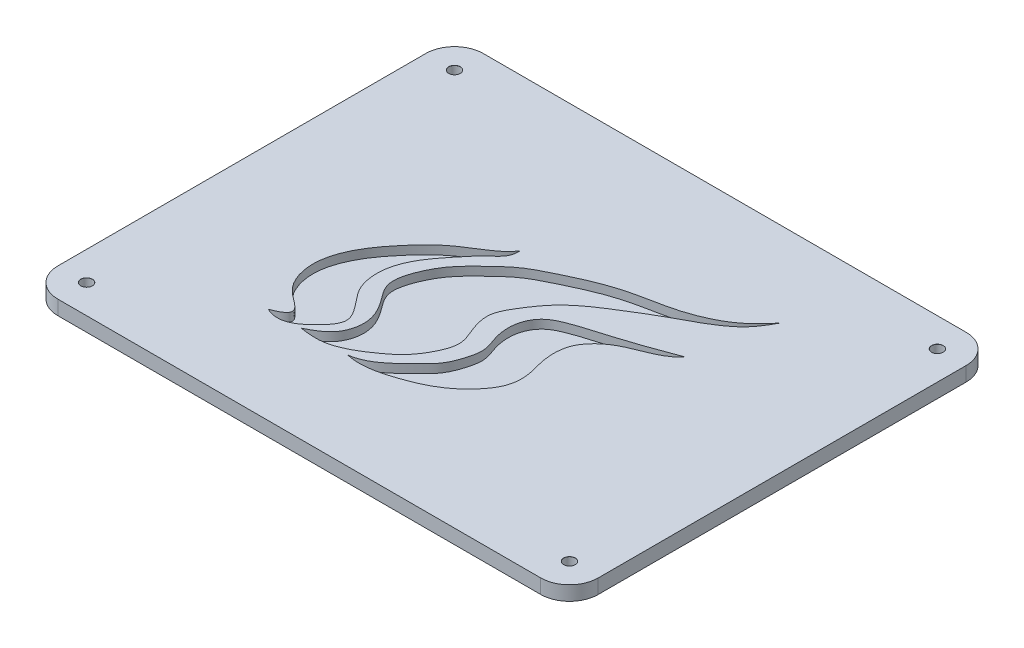
SolidWorks part; units mm, degrees
ref_plane "Plano frontal" through (0, 0, 0) normal (0, 0, 1) x (1, 0, 0)
ref_plane "Plano superior" through (0, 0, 0) normal (0, 1, 0) x (1, 0, 0)
ref_plane "Plano direito" through (0, 0, 0) normal (1, 0, 0) x (0, 0, -1)
ref_plane "Plano1" through (0, -5, 0) normal (0, -1, 0) x (1, 0, 0)
sketch "Esboço1" plane through (0, -5, 0) normal (0, -1, 0) x (1, 0, 0)
  line L0 (0, -148) -> (188, -148)
  line L1 (188, -148) -> (188, 0)
  line L2 (188, 0) -> (0, 0)
  line L3 (0, 0) -> (0, -148)
extrude "Ressalto-extrusão1" add sketch "Esboço1" against normal blind 5
sketch "Esboço2" plane through (0, -5, 0) normal (0, -1, 0) x (1, 0, 0)
  line L0 (5, -5) -> (183, -5)
  line L1 (183, -5) -> (183, -143)
  line L2 (183, -143) -> (5, -143)
  line L3 (5, -143) -> (5, -5)
extrude "Ressalto-extrusão2" add sketch "Esboço2" along normal blind 5
sketch "Esboço3" plane through (0, 0, 0) normal (0, 1, 0) x (-1, 0, 0)
  spline S0 degree 3 poles (-75.8513, -94.906) (-72.8535, -90.4619) (-63.519, -86.5735) (-53.3882, -76.0624) (-46.2023, -66.6508) (-42.9339, -55.6874) (-44.8426, -47.1017) (-50.6606, -40.2907) (-58.6418, -36.77) (-49.6316, -33.5768) knots 0 0 0 0 0.221731 0.361071 0.538534 0.656522 0.776882 0.841137 1 1 1 1
  spline S1 degree 3 poles (-49.6316, -33.5768) (-55.1932, -30.8638) (-61.3839, -35.1823) (-67.8569, -43.2627) (-64.0282, -49.8709) (-58.1961, -55.5638) (-57.0305, -66.1333) (-61.21, -75.4924) (-66.5475, -81.8637) (-71.7761, -88.296) (-76.1964, -90.9559) (-75.8513, -94.906) knots 0 0 0 0 0.190021 0.27318 0.335509 0.44453 0.578502 0.692991 0.817664 0.88529 1 1 1 1
extrude "Corte-extrusão1" cut sketch "Esboço3" against normal blind 3
sketch "Esboço4" plane through (0, 0, 0) normal (0, 1, 0) x (-1, 0, 0)
  spline S0 degree 3 poles (-136.7297, -91.7327) (-130.548, -89.419) (-121.9958, -86.2855) (-111.4177, -83.31) (-105.4901, -81.3156) (-100.2096, -78.9101) (-97.1664, -73.8232) (-96.8303, -68.8944) (-97.7553, -63.9422) (-99.9783, -59.2599) (-98.6794, -53.2404) (-96.4396, -47.1702) (-88.7973, -40.1703) (-83.295, -34.4435) (-77.2093, -33.5768) knots 0 0 0 0 0.208187 0.287593 0.345987 0.406774 0.465273 0.52264 0.558971 0.624214 0.679619 0.74702 0.825667 1 1 1 1
  spline S1 degree 3 poles (-77.2093, -33.5768) (-82.5851, -32.319) (-91.3527, -34.4282) (-101.3989, -38.5316) (-107.5302, -43.0726) (-111.3527, -47.2007) (-114.2478, -51.9233) (-114.9383, -56.8005) (-114.1515, -61.4169) (-112.8663, -65.5978) (-112.4174, -70.2105) (-113.0072, -74.7648) (-115.8896, -79.4687) (-123.6948, -85.6994) (-132.4436, -86.9091) (-136.7297, -91.7327) knots 0 0 0 0 0.166387 0.277066 0.33674 0.403034 0.451941 0.507331 0.552146 0.597486 0.643567 0.696221 0.737301 0.812803 1 1 1 1
extrude "Corte-extrusão2" cut sketch "Esboço4" against normal blind 3
ref_plane "Plano2" through (0, -9, 0) normal (0, 1, 0) x (1, 0, 0)
sketch "Esboço5" plane through (0, -9, 0) normal (0, 1, 0) x (1, 0, 0)
  spline S0 degree 3 poles (142.7977, 118.3188) (141.5574, 116.1036) (139.133, 111.7737) (133.2828, 107.1268) (127.0167, 103.5038) (120.5507, 100.1522) (114.3105, 96.3948) (108.1243, 92.5597) (102.0741, 88.4936) (96.7829, 83.3592) (92.8219, 77.3269) (88.9832, 70.7249) (90.8449, 63.3932) (94.2742, 56.7643) (91.4301, 49.5234) (87.454, 43.4921) (81.5905, 38.9932) (75.492, 35.0818) (68.3981, 32.6003) (63.5148, 33.2504) (61.0626, 33.5768) knots 0 0 0 0 0.057637 0.112657 0.168143 0.223818 0.279375 0.335006 0.390602 0.4463 0.501841 0.557867 0.611847 0.66681 0.721725 0.777322 0.832941 0.888514 0.944017 1 1 1 1
  spline S1 degree 3 poles (61.0626, 33.5768) (63.7068, 34.9359) (68.9279, 37.6195) (71.5706, 46.8653) (67.9201, 54.8174) (61.573, 61.5577) (64.0816, 70.7817) (68.2137, 78.2638) (74.4803, 84.3186) (80.7865, 90.2357) (88.5732, 94.0884) (96.3256, 97.7809) (104.4036, 100.8664) (112.8289, 102.6904) (121.3013, 104.2953) (129.403, 107.2855) (136.9905, 111.7221) (140.847, 116.1029) (142.7977, 118.3188) knots 0 0 0 0 0.062549 0.123506 0.186161 0.247751 0.310956 0.373508 0.436067 0.498651 0.561042 0.623646 0.68612 0.748656 0.811154 0.873632 0.93608 1 1 1 1
extrude "Corte-extrusão3" cut sketch "Esboço5" against normal blind 3 from surface starting at face at (106.9695, 0, -62.6548)
hole_wizard "Furo de diâmetro Ø4.0 (4)1" positions "Esboço7" profile "Esboço6" hole size "Ø4.0" standard "Ansi Metric"
sketch "Esboço7" plane through (0, 0, 0) normal (0, 1, 0) x (1, 0, 0)
  point P0 (178, 138)
  point P1 (178, 10)
  point P2 (10, 10)
  point P3 (10, 138)
sketch "Esboço6" plane through (178, 0, -138) normal (1, 0, 0) x (0, 0, 1)
  line L0 (0, 0) -> (0, 10)
  line L1 (0, 10) -> (2, 10)
  line L2 (2, 10) -> (2, 0)
  line L5 (2, 0) -> (0, 0)
  line L11 (0, -6.35) -> (0, 107.95) construction
  dimension "Thru Hole Dia." = 4
  dimension "Thru Hole Depth" = 10
chamfer "Chanfro1" distance 0.025 angle 45 4 edges at (10, 0, -136) (10, 0, -8) (178, 0, -8) (178, 0, -136)
fillet "Filete1" radius 10 8 edges at (0, -2.5, -148) (188, -2.5, 0) (188, -2.5, -148) (5, -7.5, -143) (0, -2.5, 0) (183, -7.5, -5) (5, -7.5, -5) (183, -7.5, -143) tangent propagation no
